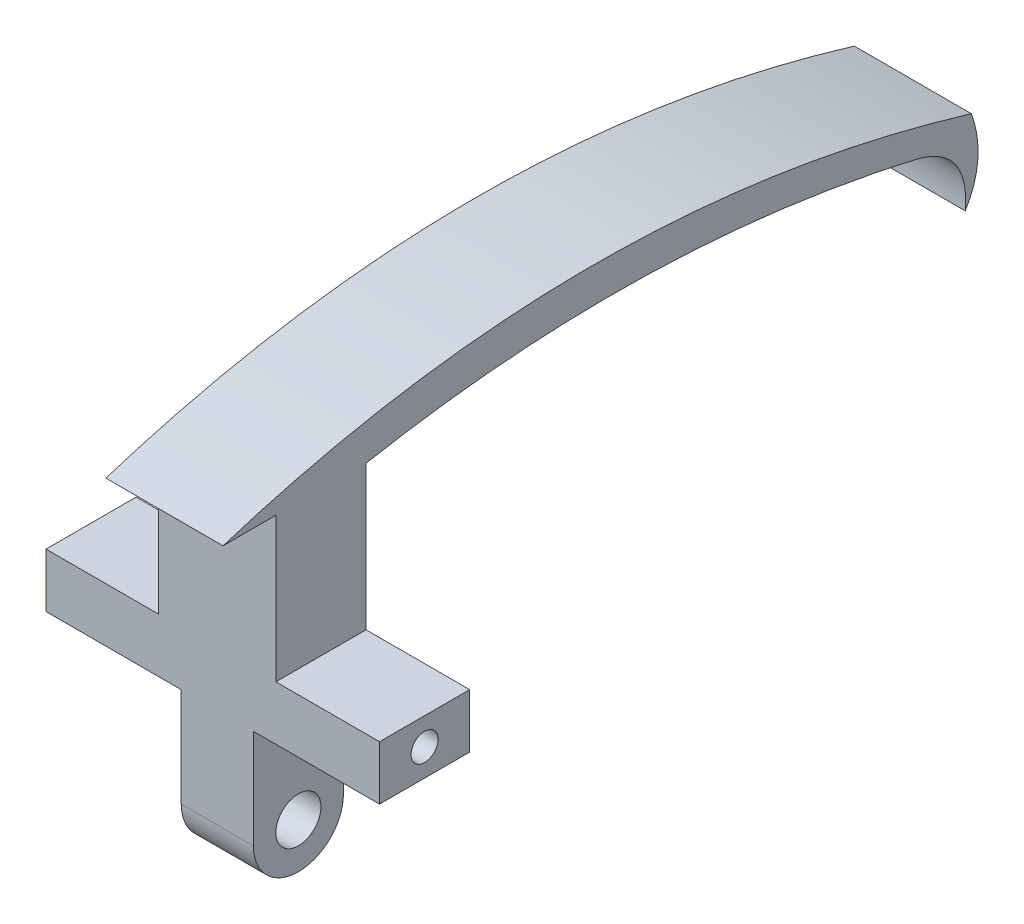
SolidWorks part; units mm, degrees
ref_plane "前视基准面" through (0, 0, 0) normal (0, 0, 1) x (1, 0, 0)
ref_plane "上视基准面" through (0, 0, 0) normal (0, 1, 0) x (1, 0, 0)
ref_plane "右视基准面" through (0, 0, 0) normal (1, 0, 0) x (0, 0, -1)
sketch "草图1" plane through (0, 0, 0) normal (0, 1, 0) x (1, 0, 0)
  line L1 (0, 0) -> (180, 0)
  line L2 (0, 0) -> (0, -50)
  line L3 (0, -50) -> (180, -50)
  line L4 (180, 0) -> (180, -50)
  dimension "D1" = 180
  dimension "D2" = 50
extrude "凸台-拉伸1" add sketch "草图1" along normal blind 30 contours L2 L1 L4 L3
sketch "草图2" plane through (0, 0, 0) normal (0, -1, 0) x (1, 0, 0)
  line L0 (90, 50) -> (90, 0) construction
  line L1 (0, 50) -> (180, 50) construction
  line L2 (0, 0) -> (180, 0) construction
  line L4 (70, 0) -> (110, 0)
  line L5 (70, 0) -> (70, 50)
  line L6 (70, 50) -> (110, 50)
  line L7 (110, 0) -> (110, 50)
  line L8 (70, 0) -> (110, 50) construction
  line L9 (70, 50) -> (110, 0) construction
  point P4 (90, 25)
  dimension "D1" = 40
extrude "凸台-拉伸2" add sketch "草图2" along normal blind 80
fillet "圆角1" radius 25 2 edges at (90, -80, 50) (90, -80, 0)
sketch "草图3" plane through (110, 0, 0) normal (1, 0, 0) x (0, 0, -1)
  line L3 (-50, 0) -> (-50, -55)
  line L4 (0, -55) -> (0, 0)
  line L5 (0, 0) -> (-50, 0)
  line L6 (-50, 0) -> (-50, -55) construction
  line L7 (0, -55) -> (0, 0) construction
  line L8 (0, 0) -> (-50, 0) construction
  circle A0 centre (-25, -55) radius 12.5
  arc A2 (-50, -55) -> (-25, -80) centre (-25, -55) ccw
  arc A3 (-25, -80) -> (0, -55) centre (-25, -55) ccw
  arc A4 (-50, -55) -> (-25, -80) centre (-25, -55) ccw construction
  arc A5 (-25, -80) -> (0, -55) centre (-25, -55) ccw construction
  dimension "D2" = 25
  dimension "D1" = 0
extrude "切除-拉伸2" cut sketch "草图3" against normal through all
sketch "草图4" plane through (0, 0, 50) normal (0, 0, 1) x (1, 0, 0)
  line L2 (90, 30) -> (90, -18.483) construction
  line L3 (0, 30) -> (180, 30) construction
  line L4 (0, 0) -> (70, 0) construction
  line L5 (7, 30) -> (32, 30)
  line L6 (7, 30) -> (7, 0)
  line L7 (7, 0) -> (32, 0)
  line L8 (32, 30) -> (32, 0)
  line L9 (0, 30) -> (0, 0) construction
  line L10 (173, 0) -> (148, 0)
  line L11 (148, 30) -> (148, 0)
  line L12 (173, 30) -> (148, 30)
  line L13 (173, 30) -> (173, 0)
  dimension "D1" = 7
  dimension "D2" = 25
sketch "草图7" plane through (0, 30, 0) normal (0, 1, 0) x (1, 0, 0)
  line L0 (7, -50) -> (32, -50) construction
  line L1 (7, -50) -> (32, -50)
  line L2 (7, -50) -> (7, 0)
  line L3 (7, 0) -> (32, 0)
  line L4 (32, -50) -> (32, 0)
  line L5 (0, 0) -> (180, 0) construction
  line L6 (173, -50) -> (148, -50) construction
  line L7 (148, -50) -> (173, -50)
  line L8 (148, -50) -> (148, 0)
  line L9 (148, 0) -> (173, 0)
  line L10 (173, -50) -> (173, 0)
  line L11 (0, -50) -> (180, -50) construction
extrude "凸台-拉伸5" add sketch "草图7" along normal blind 80 contours L2 L1 L4 L3 | L8 L7 L10 L9
sketch "草图8" plane through (173, 0, 0) normal (1, 0, 0) x (0, 0, -1)
  line L0 (0, 110) -> (-79.2937, 110)
  line L4 (-50, 30) -> (0, 30)
  line L5 (0, 30) -> (0, 110)
  line L6 (0, 110) -> (-50, 110)
  line L7 (-50, 110) -> (-50, 30)
  line L8 (-50, 30) -> (0, 30) construction
  line L9 (0, 30) -> (0, 110) construction
  line L10 (0, 110) -> (-50, 110) construction
  line L11 (-50, 110) -> (-50, 30) construction
  spline S0 degree 2 poles (-79.2937, 110) (123.3227, 174.3751) (335.8084, 110) knots 0 0 0 1 1 1
  spline S1 degree 2 poles (335.8084, 110) (344.6552, 85.0089) (332.3867, 65.0246) knots 0 0 0 1 1 1
  spline S2 degree 2 poles (332.3867, 65.0246) (334.882, 94.7931) (307.3283, 102.8847) knots 0 0 0 1 1 1
  spline S3 degree 2 poles (307.3283, 102.8847) (153.5711, 138.7084) (0, 110) knots 0 0 0 1 1 1
  dimension "D1" = 0
extrude "凸台-拉伸6" add sketch "草图8" against normal up to surface (166 mm away) up to face at (7, 70, 25)
sketch "草图9" plane through (0, 30, 0) normal (0, 1, 0) x (1, 0, 0)
  line L0 (90, -30.1798) -> (90, 231.3313) construction
  line L1 (57.5, 363.3701) -> (57.5, 32.9289) construction
  line L2 (57.5, 363.3701) -> (122.5, 363.3701) construction
  line L3 (57.5, 32.9289) -> (122.5, 32.9289) construction
  line L4 (32, -50) -> (148, -50)
  line L5 (148, -50) -> (148, 0)
  line L6 (148, 0) -> (32, 0)
  line L7 (148, -50) -> (148, 0)
  line L8 (32, -50) -> (148, -50) construction
  line L10 (148, 0) -> (32, 0) construction
  line L12 (122.5, 363.3701) -> (122.5, 32.9289) construction
  line L13 (57.5, 363.3701) -> (122.5, 32.9289) construction
  line L14 (57.5, 32.9289) -> (122.5, 363.3701) construction
  line L16 (7, -79.2937) -> (57.5, -79.2937)
  line L17 (7, -79.2937) -> (7, 350.3327)
  line L18 (7, 350.3327) -> (57.5, 350.3327)
  line L19 (32, 0) -> (32, -50)
  line L20 (32, 0) -> (32, -50)
  line L21 (57.5, -79.2937) -> (57.5, 350.3327)
  line L22 (122.5, 350.3327) -> (173, 350.3327)
  line L23 (122.5, 350.3327) -> (122.5, -79.2937)
  line L24 (122.5, -79.2937) -> (173, -79.2937)
  line L25 (173, 350.3327) -> (173, -79.2937)
  point P7 (90, 198.1495)
  point P14 (90, 0)
  line M10 (32, -50) -> (148, -50)
  line M11 (148, -50) -> (148, 0)
  line M12 (148, 0) -> (32, 0)
  line M13 (32, 0) -> (32, -50)
  dimension "D2" = 65
  dimension "D1" = 0
extrude "切除-拉伸3" cut sketch "草图9" along normal through all contours L16 L21 L18 L17 M10 M13 M12 | L25 L22 L23 L24 M12 M11 M10 | L21 M10 M12 M13 | L23 M12 M10 M11 region at (44.75, 30, 25) region at (31.4696, 30, -145.5416) region at (135.25, 30, 25) region at (148.5304, 30, -145.5416)
sketch "草图10" plane through (0, 110, 0) normal (0, -1, 0) x (1, 0, 0)
  line L0 (57.5, 79.2937) -> (57.5, 0) construction
  line L1 (57.5, 50) -> (122.5, 50)
  line L2 (57.5, 50) -> (57.5, 0)
  line L3 (57.5, 0) -> (122.5, 0)
  line L4 (180, 0) -> (180, 50)
  line L5 (0, 0) -> (180, 0)
  line L6 (0, 50) -> (0, 0)
  line L7 (180, 50) -> (0, 50)
  line L8 (180, 0) -> (180, 50) construction
  line L9 (0, 0) -> (180, 0) construction
  line L10 (0, 50) -> (0, 0) construction
  line L11 (180, 50) -> (0, 50) construction
  line L12 (122.5, 50) -> (122.5, 0)
  dimension "D1" = 0
extrude "凸台-拉伸7" add sketch "草图10" along normal up to surface (80 mm away) up to face at (90, 30, 25)
sketch "草图11" plane through (0, 0, 0) normal (-1, 0, 0) x (0, 0, 1)
  line L4 (0, 0) -> (50, 0)
  line L5 (50, 0) -> (50, 30)
  line L6 (50, 30) -> (0, 30)
  line L7 (0, 30) -> (0, 0)
  line L8 (0, 0) -> (50, 0)
  line L9 (50, 0) -> (50, 30)
  line L10 (50, 30) -> (0, 30)
  line L11 (0, 30) -> (0, 0)
  dimension "D1" = 0
extrude "凸台-拉伸8" add sketch "草图11" along normal blind 10
sketch "草图12" plane through (-10, 0, 0) normal (-1, 0, 0) x (0, 0, 1)
  line L4 (0, 30) -> (0, 0)
  line L5 (0, 0) -> (50, 0)
  line L6 (50, 0) -> (50, 30)
  line L7 (50, 30) -> (0, 30)
  line L8 (0, 30) -> (0, 0)
  line L9 (0, 0) -> (50, 0)
  line L10 (50, 0) -> (50, 30)
  line L11 (50, 30) -> (0, 30)
  dimension "D1" = 0
extrude "切除-拉伸4" cut sketch "草图12" against normal blind 5
sketch "草图13" plane through (-5, 0, 0) normal (-1, 0, 0) x (0, 0, 1)
  line L0 (0, 15) -> (85.5533, 15) construction
  line L1 (0, 30) -> (0, 0) construction
  line L2 (25, 30) -> (25, 15) construction
  line L3 (50, 30) -> (0, 30) construction
  circle A0 centre (25, 15) radius 7.5
  dimension "D1" = 15
extrude "切除-拉伸5" cut sketch "草图13" against normal through all
